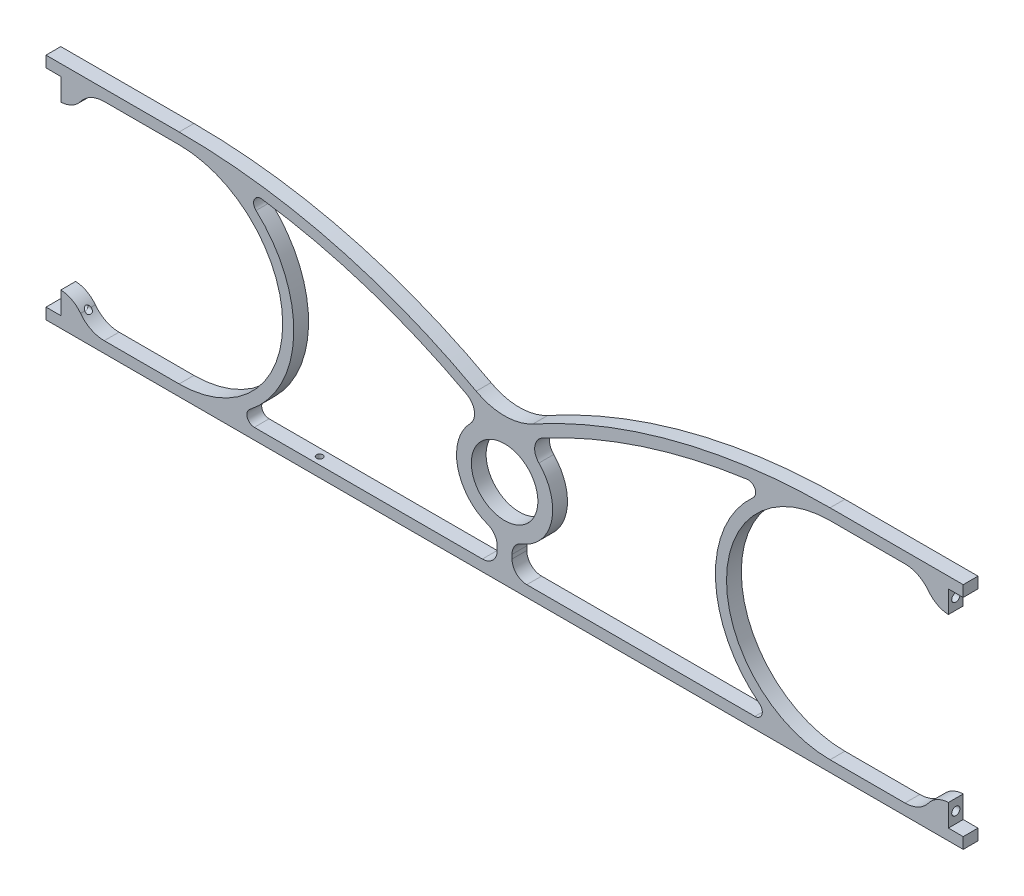
SolidWorks part; units mm, degrees
material "6061-T6 (SS)"
ref_plane "Front Plane" through (0, 0, 0) normal (0, 0, 1) x (1, 0, 0)
ref_plane "Top Plane" through (0, 0, 0) normal (0, 1, 0) x (1, 0, 0)
ref_plane "Right Plane" through (0, 0, 0) normal (1, 0, 0) x (0, 0, -1)
sketch "Sketch1" plane through (0, 0, 0) normal (0, 0, 1) x (1, 0, 0)
  line L0 (190.5, -38.1) -> (-190.5, -38.1)
  line L1 (-190.5, -38.1) -> (-190.5, -33.3375)
  line L2 (-190.5, -33.3375) -> (-118.5797, -33.3375)
  line L3 (0, 0) -> (0, 58.9425) construction
  line L4 (0, 0) -> (-90.0269, 0) construction
  line L5 (-190.5, 60.325) -> (-190.5, 55.5625)
  line L6 (-190.5, 60.325) -> (-139.7, 60.325)
  line L7 (-190.5, 55.5625) -> (-139.7, 55.5625)
  line L8 (-190.5, 11.1125) -> (-109.7015, 11.1125) construction
  line L9 (190.5, 60.325) -> (190.5, 55.5625)
  line L10 (190.5, -38.1) -> (190.5, -33.3375)
  line L11 (190.5, -33.3375) -> (-118.5797, -33.3375)
  line L12 (190.5, 60.325) -> (139.7, 60.325)
  line L13 (190.5, 55.5625) -> (139.7, 55.5625)
  line L14 (-190.5, 55.5625) -> (-196.85, 55.5625)
  line L15 (-196.85, 55.5625) -> (-196.85, 60.325)
  line L16 (-196.85, 60.325) -> (-190.5, 60.325)
  line L17 (-190.5, -33.3375) -> (-196.85, -33.3375)
  line L18 (-196.85, -33.3375) -> (-196.85, -38.1)
  line L19 (-196.85, -38.1) -> (-190.5, -38.1)
  line L20 (196.85, -38.1) -> (190.5, -38.1)
  line L21 (190.5, -33.3375) -> (196.85, -33.3375)
  line L22 (196.85, -33.3375) -> (196.85, -38.1)
  line L23 (196.85, 60.325) -> (190.5, 60.325)
  line L24 (196.85, 55.5625) -> (196.85, 60.325)
  line L25 (190.5, 55.5625) -> (196.85, 55.5625)
  line L26 (-3.175, -20.3918) -> (-3.175, -33.3375)
  line L27 (3.175, -20.3918) -> (3.175, -33.3375)
  circle A0 centre (0, 0) radius 14.2875
  circle A1 centre (0, 0) radius 20.6375
  arc A2 (-139.7, -33.3375) -> (-139.7, 55.5625) centre (-139.7, 11.1125) ccw
  arc A3 (-118.5797, -33.3375) -> (-116.5356, 54.5323) centre (-139.7, 11.1125) ccw
  circle A4 centre (-139.7, 11.1125) radius 49.2125 construction
  circle A5 centre (-139.7, 11.1125) radius 44.45 construction
  arc A6 (0, 20.6375) -> (-139.7, 60.325) centre (-139.7, -205.3908) ccw
  arc A7 (-7.1163, 19.3717) -> (-139.7, 55.5625) centre (-139.7, -205.3908) ccw
  arc A8 (118.5797, -33.3375) -> (116.5356, 54.5323) centre (139.7, 11.1125) cw
  arc A9 (139.7, -33.3375) -> (139.7, 55.5625) centre (139.7, 11.1125) cw
  arc A10 (7.1163, 19.3717) -> (139.7, 55.5625) centre (139.7, -205.3908) cw
  arc A11 (0, 20.6375) -> (139.7, 60.325) centre (139.7, -205.3908) cw
  dimension "D1" = 4.7625
  dimension "D2" = 28.575
  dimension "D3" = 6.35
  dimension "D5" = 4.7625
  dimension "D7" = 50.8
  dimension "D4" = 381
  dimension "D6" = 88.9
  dimension "D8" = 6.35
  dimension "D9" = 38.1
  dimension "D10" = 6.35
extrude "Boss-Extrude1" add sketch "Sketch1" against normal blind 6.35 contours L18 L19 L1 L17 | L10 L11 L2 L1 L0 | A3 A7 A2 L2 | L16 L15 L14 L5 | A7 A1 A6 L6 L5 L7 | A1 A0 | A1 L26 L11 L27 | A11 A1 A10 L13 L9 L12 | A10 A8 L11 A9 | L9 L25 L24 L23 | L22 L21 L10 L20 region at (0, -35.7188, 0) region at (193.675, -35.7188, 0) region at (-193.675, -35.7188, 0) region at (129.1398, -32.3214, 0) region at (-94.2339, 11.1125, 0) region at (128.0198, 57.2514, 0) region at (-165.1, 57.511, 0) region at (0, -26.9464, 0) region at (193.675, 57.9437, 0) region at (-193.675, 57.9437, 0) region at (0, -20.0538, 0)
sketch "Sketch2" plane through (0, 0, 0) normal (0, 0, 1) x (1, 0, 0)
  line L0 (-190.5, 55.5625) -> (-190.5, 46.0375)
  line L2 (-196.85, 55.5625) -> (-139.7, 55.5625) construction
  line L3 (-190.5, 46.0375) -> (-184.15, 46.0375)
  line L4 (-184.15, 46.0375) -> (-184.15, 55.5625)
  line L7 (-184.15, 55.5625) -> (-190.5, 55.5625)
  line L8 (-190.5, -33.3375) -> (-190.5, -23.8125)
  line L9 (-196.85, -33.3375) -> (-139.7, -33.3375) construction
  line L11 (-190.5, -23.8125) -> (-184.15, -23.8125)
  line L12 (-184.15, -23.8125) -> (-184.15, -33.3375)
  line L13 (-184.15, -33.3375) -> (-190.5, -33.3375)
  line L14 (-196.85, 55.5625) -> (-196.85, 60.325) construction
  line L15 (0, 0) -> (0, 66.1526) construction
  line L16 (184.15, -33.3375) -> (190.5, -33.3375)
  line L17 (184.15, -23.8125) -> (184.15, -33.3375)
  line L18 (190.5, -23.8125) -> (184.15, -23.8125)
  line L19 (190.5, -33.3375) -> (190.5, -23.8125)
  line L20 (184.15, 55.5625) -> (190.5, 55.5625)
  line L21 (184.15, 46.0375) -> (184.15, 55.5625)
  line L22 (190.5, 46.0375) -> (184.15, 46.0375)
  line L23 (190.5, 55.5625) -> (190.5, 46.0375)
  line L24 (-184.15, -33.3375) -> (-190.5, -33.3375)
  line M22 (196.85, -33.3375) -> (139.7, -33.3375)
  line M24 (139.7, 55.5625) -> (196.85, 55.5625)
  line M32 (-196.85, 55.5625) -> (-139.7, 55.5625)
  line M34 (-139.7, -33.3375) -> (-196.85, -33.3375)
  dimension "D1" = 6.35
  dimension "D2" = 6.35
  dimension "D3" = 9.525
extrude "Boss-Extrude2" add sketch "Sketch2" against normal up to surface (6.35 mm away) contours L12 L11 L8 M34 | L3 L4 L0 M32 | L23 L21 L22 M24 | L19 L18 L17 M22 region at (-187.325, 50.8, 0) region at (-187.325, -28.575, 0) region at (187.325, -28.575, 0) region at (187.325, 50.8, 0) up to face at (-46.9913, -1.8438, -6.35)
fillet "Fillet1" radius 12.7 4 edges at (184.15, -33.3375, -3.175) (184.15, 55.5625, -3.175) (-184.15, -33.3375, -3.175) (-184.15, 55.5625, -3.175)
fillet "Fillet2" radius 11.1125 4 edges at (184.15, -23.8125, -3.175) (184.15, 46.0375, -3.175) (-184.15, -23.8125, -3.175) (-184.15, 46.0375, -3.175)
hole_wizard "#6-32 Tapped Hole1" positions "Sketch4" profile "Sketch3" tap size "#6-32" standard "ANSI Inch"
sketch "Sketch4" plane through (0, -38.1, 0) normal (0, -1, 0) x (-1, 0, 0)
  line L2 (196.85, 3.175) -> (-196.85, 3.175) construction
  line L3 (196.85, 6.35) -> (196.85, 0) construction
  line L4 (-196.85, 6.35) -> (-196.85, 0) construction
  point P14 (82.55, 3.175)
  dimension "D1" = 114.3
sketch "Sketch3" plane through (-82.55, -38.1, -3.175) normal (1, 0, 0) x (0, 0, -1)
  line L0 (0, 0) -> (0, 10.2107)
  line L1 (0, 10.2107) -> (1.3525, 9.398)
  line L2 (1.3525, 9.398) -> (1.3525, 0)
  line L5 (1.3525, 0) -> (0, 0)
  line L10 (0, 10.2107) -> (-1.3526, 9.398) construction
  line L11 (0, -6.35) -> (0, 107.95) construction
  dimension "Tap Drill Dia." = 2.7051
  dimension "Tap Drill Depth" = 9.398
  dimension "Drill Angle" = 118
cosmetic thread "Hole Thread1" parameters "D1"=4.7625, "D2"=3.5052
sketch "Sketch6" plane through (0, 0, 0) normal (0, 0, 1) x (1, 0, 0)
  line L0 (0, 0) -> (-39.9561, 39.9561) construction
  line L1 (0, 0) -> (48.4711, 48.4711) construction
  line L2 (0, 0) -> (-40.8602, -40.8602) construction
  line L3 (0, 0) -> (51.2771, -51.2771) construction
  line L4 (0, 0) -> (0, 63.9221) construction
  circle A0 centre (-20.4301, 20.4301) radius 1.8986
  circle A1 centre (20.4301, 20.4301) radius 1.8986
  circle A2 centre (-20.4301, -20.4301) radius 1.8986
  circle A3 centre (20.4301, -20.4301) radius 1.8986
  circle A4 centre (0, 0) radius 28.8925 construction
  circle A5 centre (0, 0) radius 31.75 construction
  dimension "D5" = 57.785
  dimension "D6" = 3.7973
  dimension "D7" = 3.7973
  dimension "D8" = 3.7973
  dimension "D9" = 3.7973
  dimension "D10" = 63.5
  dimension "D1" = 90
  dimension "D2" = 45
  dimension "D3" = 90
  dimension "D4" = 90
fillet "Fillet3" radius 25.4 1 edges at (0, 20.6375, -3.175)
fillet "Fillet4" radius 6.35 6 edges at (-3.175, -33.3375, -3.175) (3.175, -33.3375, -3.175) (3.175, -20.3918, -3.175) (-3.175, -20.3918, -3.175) (7.1163, 19.3717, -3.175) (-7.1163, 19.3717, -3.175)
fillet "Fillet5" radius 3.175 4 edges at (118.5797, -33.3375, -3.175) (116.5356, 54.5323, -3.175) (-118.5797, -33.3375, -3.175) (-116.5356, 54.5323, -3.175)
hole_wizard "#6-32 Tapped Hole2" positions "Sketch8" profile "Sketch7" tap size "#6-32" standard "ANSI Inch"
sketch "Sketch8" plane through (190.5, 0, 0) normal (1, 0, 0) x (0, 0, -1)
  line L0 (0, 50.8) -> (6.35, 50.8) construction
  line L1 (0, 55.5625) -> (0, 46.0375) construction
  line L2 (6.35, 46.0375) -> (6.35, 55.5625) construction
  line L5 (0, -28.575) -> (6.35, -28.575) construction
  line L6 (0, -33.3375) -> (0, -23.8125) construction
  line L7 (6.35, -23.8125) -> (6.35, -33.3375) construction
  point P20 (3.175, -28.575)
  point P22 (3.175, 50.8)
sketch "Sketch7" plane through (190.5, -28.575, -3.175) normal (0, 1, 0) x (0, 0, -1)
  line L0 (0, 0) -> (0, 10.2107)
  line L1 (0, 10.2107) -> (1.3525, 9.398)
  line L2 (1.3525, 9.398) -> (1.3525, 7.112)
  line L3 (1.3525, 7.112) -> (1.7526, 7.112)
  line L4 (1.7526, 7.112) -> (1.7526, 0)
  line L5 (1.7526, 0) -> (0, 0)
  line L10 (0, 10.2107) -> (-1.3526, 9.398) construction
  line L11 (0, -6.35) -> (0, 107.95) construction
  dimension "Tap Drill Dia." = 2.7051
  dimension "Tap Drill Depth" = 9.398
  dimension "Thread Major Dia." = 3.5052
  dimension "Thread Depth" = 7.112
  dimension "Drill Angle" = 118
mirror "Mirror1" about plane through (0, 0, 0) normal (1, 0, 0) of "#6-32 Tapped Hole2"
